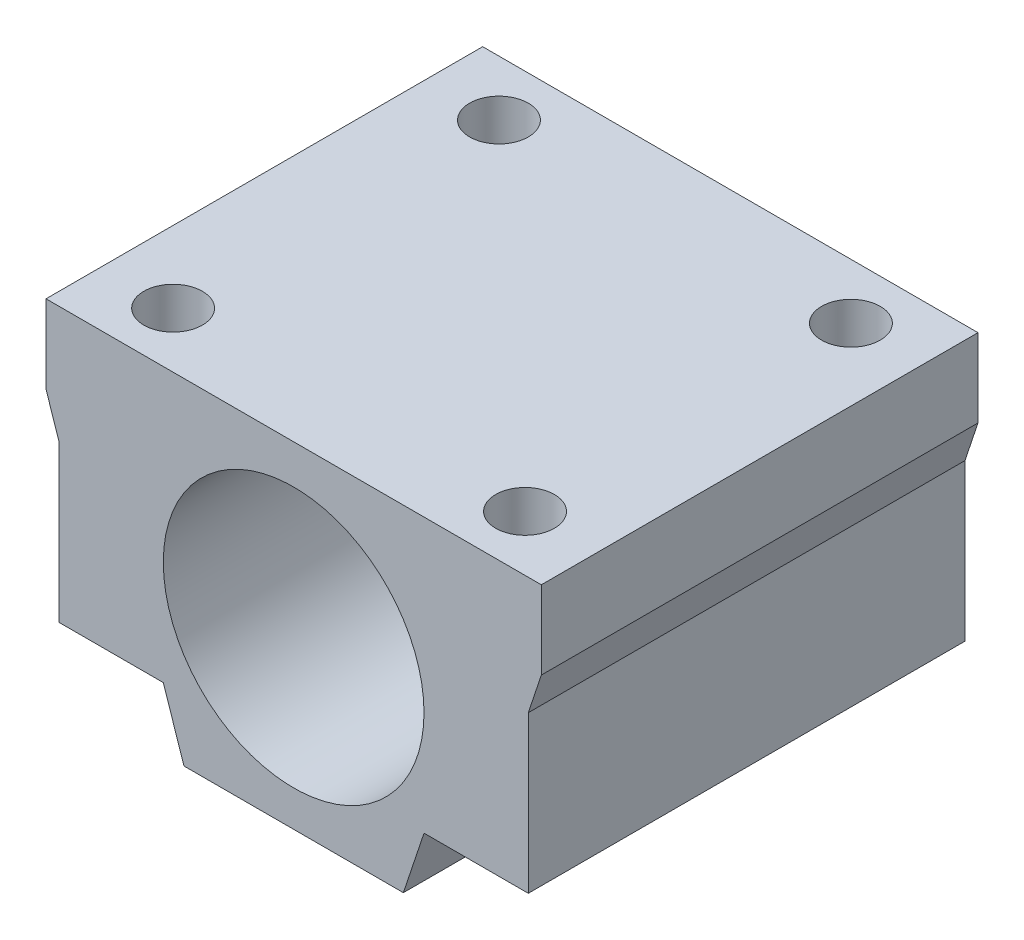
SolidWorks part; units mm, degrees
ref_plane "Płaszczyzna przednia" through (0, 0, 0) normal (0, 0, 1) x (1, 0, 0)
ref_plane "Płaszczyzna górna" through (0, 0, 0) normal (0, 1, 0) x (1, 0, 0)
ref_plane "Płaszczyzna prawa" through (0, 0, 0) normal (1, 0, 0) x (0, 0, -1)
sketch "Szkic1" plane through (0, 0, 0) normal (0, 0, 1) x (1, 0, 0)
  line L0 (0, 27.8768) -> (0, -25.5) construction
  line L1 (-45.0718, 0) -> (45.0718, 0) construction
  line L2 (16.8333, -25.5) -> (-16.8333, -25.5)
  line L3 (-16.8333, -25.5) -> (-20, -16)
  line L4 (-20, -16) -> (-36, -16)
  line L5 (-36, -16) -> (-36, 8)
  line L6 (-36, 8) -> (-38, 14)
  line L7 (-38, 14) -> (-38, 26)
  line L8 (-38, 26) -> (38, 26)
  line L9 (-20, 33.7923) -> (-20, -60.7077) construction
  line L10 (16.8333, -25.5) -> (20, -16)
  line L11 (20, -16) -> (36, -16)
  line L12 (36, -16) -> (36, 8)
  line L13 (36, 8) -> (38, 14)
  line L14 (38, 14) -> (38, 26)
  circle A0 centre (0, 0) radius 20
  point P24 (0, 26)
  dimension "D6" = 40
  dimension "D1" = 42
  dimension "D2" = 12
  dimension "D3" = 38
  dimension "D4" = 18
  dimension "D5" = 51.5
  dimension "D7" = 26
  dimension "D8" = 2
extrude "Dodanie-wyciągnięcie1" add sketch "Szkic1" along normal blind 33.5 and the other way blind 33.5
hole_wizard "Otwór pod śrubę M81" positions "Szkic14" profile "Szkic15" hole size "M8" standard "ISO" end condition through all
sketch "Szkic14" plane through (0, -16, 0) normal (0, -1, 0) x (-1, 0, 0)
  line L0 (-55.4076, 0) -> (69.9836, 0) construction
  line L1 (0, -40.4436) -> (0, 48.2944) construction
  point P0 (-27, -25)
  dimension "D1" = 54
  dimension "D2" = 50
sketch "Szkic15" plane through (27, -16, 25) normal (1, 0, 0) x (0, 0, -1)
  line L0 (0, 0) -> (0, 42)
  line L1 (0, 42) -> (4.5, 42)
  line L2 (4.5, 42) -> (4.5, 0)
  line L5 (4.5, 0) -> (0, 0)
  line L11 (0, -6.35) -> (0, 107.95) construction
  dimension "Średnica otworu na wylot" = 9
  dimension "Głębokość otworu na wylot" = 42
mirror "Lustro1" about plane through (0, 0, 0) normal (1, 0, 0) of "Otwór pod śrubę M81"
mirror "Lustro2" about plane through (0, 0, 0) normal (0, 0, 1) of "Otwór pod śrubę M81", "Lustro1"
